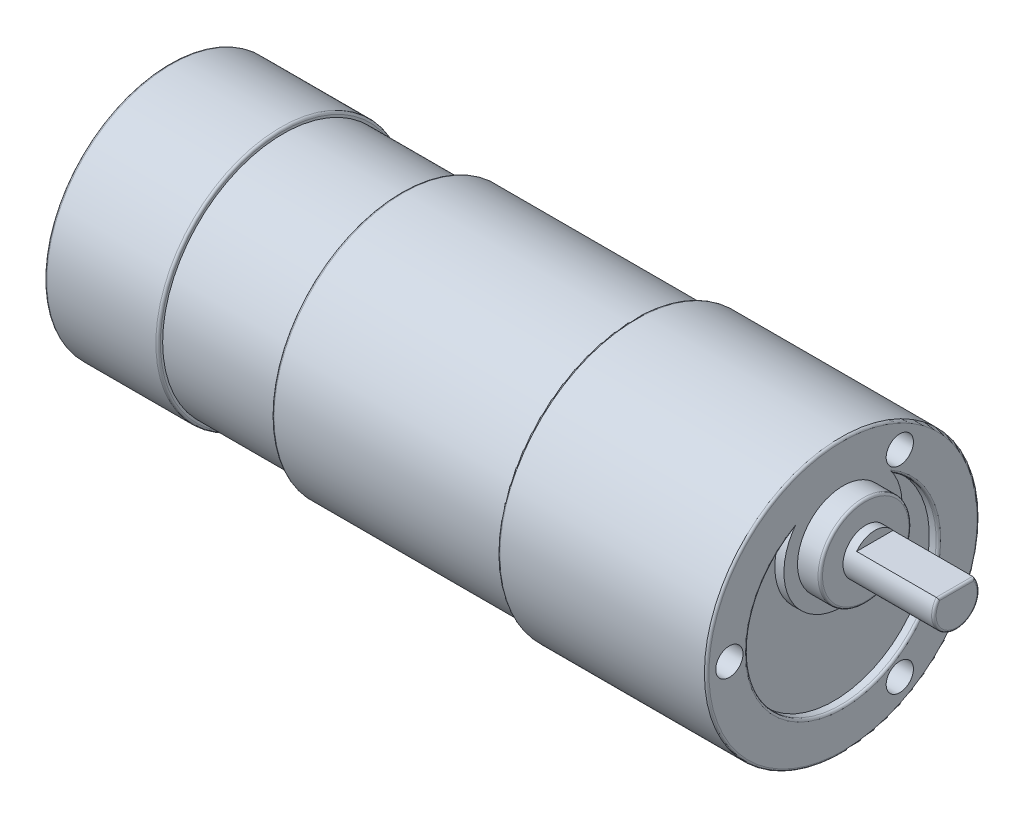
SolidWorks part; units mm, degrees
other "Camera1"
material "1060 Alloy"
ref_plane "Front Plane" through (0, 0, 0) normal (0, 0, 1) x (1, 0, 0)
ref_plane "Top Plane" through (0, 0, 0) normal (0, 1, 0) x (1, 0, 0)
ref_plane "Right Plane" through (0, 0, 0) normal (1, 0, 0) x (0, 0, -1)
sketch "Sketch1" plane through (0, 0, 0) normal (1, 0, 0) x (0, 0, -1)
  circle A0 centre (0, 0) radius 15
  dimension "D1" = 30
extrude "Boss-Extrude1" add sketch "Sketch1" along normal blind 76.6
sketch "Sketch2" plane through (76.6, 0, 0) normal (1, 0, 0) x (0, 0, -1)
  line L0 (0, 0) -> (0, 5.5) construction
  circle A0 centre (0, 5.5) radius 2.5
  dimension "D1" = 5
  dimension "D2" = 5.5
extrude "Boss-Extrude2" add sketch "Sketch2" along normal blind 10
sketch "Sketch4" plane through (86.6, 0, 0) normal (1, 0, 0) x (0, 0, -1)
  line L0 (-2, 7) -> (2, 7)
  line L1 (0, 5.5) -> (0, 7) construction
  arc A0 (2, 7) -> (-2, 7) centre (0, 5.5) ccw
  circle A1 centre (0, 5.5) radius 2.5 construction
  dimension "D1" = 1.5
extrude "Cut-Extrude1" cut sketch "Sketch4" against normal blind 9
sketch "Sketch5" plane through (0, 0, 0) normal (0, 0, 1) x (1, 0, 0)
  line L0 (0, 0) -> (76.6, 0) construction
  line L1 (76.6, -15) -> (76.6, 15) construction
  line L2 (76.6, 5.5) -> (86.6, 5.5) construction
  line L3 (76.6, 3) -> (76.6, 8) construction
  line L4 (86.6, 3) -> (86.6, 7) construction
  line L6 (0, 13.75) -> (12.5, 13.75)
  line L7 (0, 15) -> (0, -15) construction
  line L8 (12.5, 13.75) -> (12.5, 13.25)
  line L9 (12.5, 13.25) -> (25.5, 13.25)
  line L10 (25.5, 13.25) -> (25.5, 14.25)
  line L11 (25.5, 14.25) -> (51.1, 14.25)
  line L12 (51.1, 14.25) -> (51.1, 15)
  line L13 (76.6, 15) -> (0, 15) construction
  line L14 (51.1, 15) -> (0, 15)
  line L15 (0, 15) -> (0, 13.75)
  dimension "D1" = 0.75
  dimension "D2" = 1.25
  dimension "D3" = 0.5
  dimension "D4" = 12.5
  dimension "D5" = 13
  dimension "D6" = 25.6
ref_axis "Axis1" through (-4.33, 0, 0) along (1, 0, 0)
revolve "Cut-Revolve1" cut sketch "Sketch5" angle 360 about axis through (-4.33, 0, 0) along (1, 0, 0)
sketch "Sketch6" plane through (76.6, 0, 0) normal (1, 0, 0) x (0, 0, -1)
  circle A0 centre (0, 0) radius 15
  circle A1 centre (0, 5.5) radius 5
  dimension "D1" = 10
  dimension "D2" = 30
extrude "Cut-Extrude2" cut sketch "Sketch6" against normal blind 2.5
sketch "Sketch7" plane through (74.1, 0, 0) normal (1, 0, 0) x (0, 0, -1)
  circle A0 centre (0, 0) radius 10.5
  circle A1 centre (0, 5.5) radius 6.5
  circle A2 centre (0, 5.5) radius 5 construction
  dimension "D1" = 1.5
extrude "Cut-Extrude3" cut sketch "Sketch7" against normal blind 1 contours A1 A0 region at (74.1, -2.6501, 0)
sketch "Sketch8" plane through (74.1, 0, 0) normal (1, 0, 0) x (0, 0, -1)
  line L0 (0, 0) -> (15, 0) construction
  line L1 (0, 0) -> (6.25, 10.8253) construction
  circle A0 centre (0, 0) radius 12.5 construction
  circle A1 centre (6.25, 10.8253) radius 1.5
  circle A2 centre (0, 0) radius 15 construction
  circle A3 centre (6.25, -10.8253) radius 1.5
  circle A4 centre (-12.5, 0) radius 1.5
  point P5 (0, 0)
  dimension "D1" = 25
  dimension "D3" = 3
  dimension "D2" = 60
  dimension "D4" = 3
extrude "Cut-Extrude4" cut sketch "Sketch8" against normal blind 4
fillet "Fillet1" radius 0.25 9 edges at (86.6, 7, 0) (86.6, 3, 0) (76.6, 5.5, -5) (12.5, 0, 13.75) (25.5, 0, 14.25) (51.1, 0, 15) (0, 0, 13.75) (74.1, 0, -15) (74.1, -10.5, 0)
